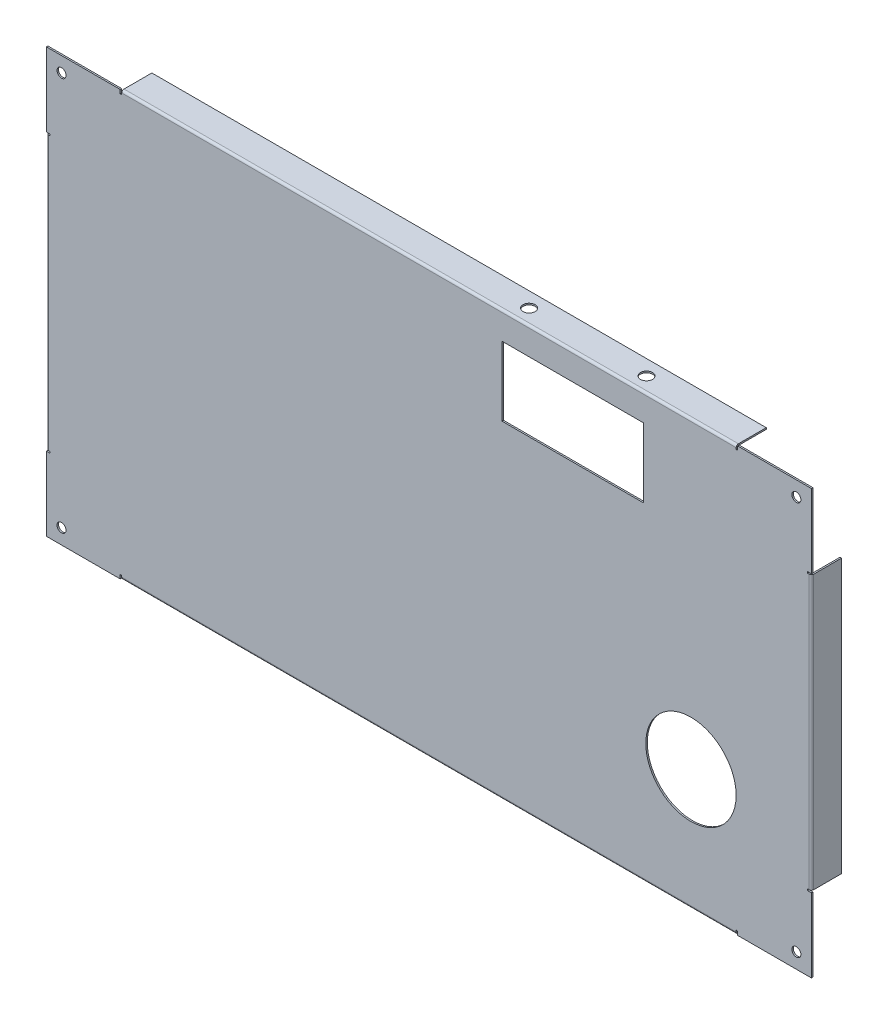
SolidWorks part; units mm, degrees
note: The reader was unsure of these and kept them because the rebuilt part matched: thickness of "基体-法兰1", "边线-法兰1", "边线-法兰2", "边线-法兰3", "边线-法兰4", "钣金1", "钣金6", "钣金7", "钣金8", "钣金9", "钣金10"; flange length of "边线-法兰1", "边线-法兰2", "边线-法兰3", "边线-法兰4".
ref_plane "前视基准面" through (0, 0, 0) normal (0, 0, 1) x (1, 0, 0)
ref_plane "上视基准面" through (0, 0, 0) normal (0, 1, 0) x (1, 0, 0)
ref_plane "右视基准面" through (0, 0, 0) normal (1, 0, 0) x (0, 0, -1)
sketch "草图1" plane through (0, 0, 0) normal (0, 0, 1) x (1, 0, 0)
  line L1 (-254, -140.75) -> (254, -140.75)
  line L2 (-254, -140.75) -> (-254, 140.75)
  line L3 (-254, 140.75) -> (254, 140.75)
  line L4 (254, -140.75) -> (254, 140.75)
  line L5 (-254, -140.75) -> (254, 140.75) construction
  line L6 (-254, 140.75) -> (254, -140.75) construction
  line L7 (48.5, 122.75) -> (142.5, 122.75)
  line L8 (48.5, 122.75) -> (48.5, 76.75)
  line L9 (48.5, 76.75) -> (142.5, 76.75)
  line L10 (142.5, 122.75) -> (142.5, 76.75)
  circle A0 centre (-244, 130.75) radius 3
  circle A1 centre (-244, -130.75) radius 3
  circle A2 centre (244, 130.75) radius 3
  circle A3 centre (244, -130.75) radius 3
  circle A4 centre (174, -60.75) radius 30
  point P0 (0, 0)
  dimension "D11" = 6
  dimension "D14" = 60
  dimension "D1" = 508
  dimension "D2" = 281.5
  dimension "D3" = 10
  dimension "D4" = 10
  dimension "D5" = 10
  dimension "D6" = 10
  dimension "D7" = 10
  dimension "D8" = 10
  dimension "D9" = 10
  dimension "D10" = 10
  dimension "D12" = 80
  dimension "D13" = 80
  dimension "D15" = 46
  dimension "D16" = 94
  dimension "D17" = 64
  dimension "D18" = 111.5
base flange "基体-法兰1" sketch "草图1" thickness 1 reverse thickness direction no parameters "D1"=0.5
edge flange "边线-法兰1" sketch "草图22" flange angle 90 flange length 20 flange position material inside bend radius 0.5 thickness 1 relief rectangular parameters "D6"=10
sketch "草图22" plane through (0, 140.75, -1) normal (0, 1, 0) x (1, 0, 0)
  line L2 (-204, 0) -> (-204, 19)
  line L3 (-204, 19) -> (204, 19)
  line L4 (204, 19) -> (204, 0)
  line L5 (254, 0) -> (-254, 0) construction
  line L6 (204, 0) -> (-204, 0)
  line L7 (-254, 0) -> (-254, -1) construction
  line L8 (254, 0) -> (254, -1) construction
  dimension "D1" = 50
  dimension "D2" = 50
bend "边线折弯1" bend radius 0.5 bend angle 90 parameters "D5"=1
edge flange "边线-法兰2" sketch "草图25" flange angle 90 flange length 20 flange position material inside bend radius 0.5 thickness 1 relief rectangular parameters "D6"=10
sketch "草图25" plane through (-254, 0, -1) normal (-1, 0, 0) x (0, 1, 0)
  line L0 (140.75, 0) -> (-140.75, 0) construction
  line L1 (90.75, 0) -> (-90.75, 0)
  line L2 (-90.75, 0) -> (-90.75, 19)
  line L3 (-90.75, 19) -> (90.75, 19)
  line L4 (90.75, 19) -> (90.75, 0)
  line L5 (140.75, 0) -> (140.75, -1) construction
  line L6 (-140.75, 0) -> (-140.75, -1) construction
  dimension "D1" = 50
  dimension "D2" = 50
bend "边线折弯2" bend radius 0.5 bend angle 90 parameters "D5"=2
edge flange "边线-法兰3" sketch "草图28" flange angle 90 flange length 20 flange position material inside bend radius 0.5 thickness 1 relief rectangular parameters "D6"=10
sketch "草图28" plane through (0, -140.75, -1) normal (0, -1, 0) x (-1, 0, 0)
  line L2 (-204, 0) -> (-204, 19)
  line L3 (-204, 19) -> (204, 19)
  line L4 (204, 19) -> (204, 0)
  line L7 (254, 0) -> (-254, 0) construction
  line L8 (204, 0) -> (-204, 0)
  line L9 (254, 0) -> (254, -1) construction
  line L10 (-254, 0) -> (-254, -1) construction
  dimension "D1" = 50
  dimension "D2" = 50
bend "边线折弯3" bend radius 0.5 bend angle 90 parameters "D5"=3
edge flange "边线-法兰4" sketch "草图31" flange angle 90 flange length 20 flange position material inside bend radius 0.5 thickness 1 relief rectangular parameters "D6"=10
sketch "草图31" plane through (254, 0, -1) normal (1, 0, 0) x (0, -1, 0)
  line L2 (-90.75, 0) -> (-90.75, 19)
  line L3 (-90.75, 19) -> (90.75, 19)
  line L4 (90.75, 19) -> (90.75, 0)
  line L5 (140.75, 0) -> (-140.75, 0) construction
  line L6 (90.75, 0) -> (-90.75, 0)
  line L7 (140.75, 0) -> (140.75, -1) construction
  line L8 (-140.75, 0) -> (-140.75, -1) construction
  dimension "D1" = 50
  dimension "D2" = 50
bend "边线折弯4" bend radius 0.5 bend angle 90 parameters "D5"=4
sketch "草图32" plane through (0, 139.75, 0) normal (0, -1, 0) x (-1, 0, 0)
  circle A0 centre (-134.5, 10) radius 4
  circle A1 centre (-56.5, 10) radius 4
  dimension "D1" = 8
extrude "切除-拉伸1" cut sketch "草图32" against normal through all normal cut yes
sketch "折弯-线1" plane through (0, 0, 0) normal (0, 1, 0) x (1, 0, 0)
sketch "边界框1" plane through (0, 0, 0) normal (0, 1, 0) x (1, 0, 0)
sheet metal parameters "钣金1" thickness 1 parameters "D1"=0.5
flat pattern "平板型式1" [suppressed]
sketch "折弯-线2" plane through (0, 0, 0) normal (0, 1, 0) x (1, 0, 0)
sketch "边界框2" [suppressed] plane through (0, 0, 0) normal (0, 1, 0) x (1, 0, 0)
sheet metal parameters "钣金6" thickness 1 parameters "D1"=0.5, "D7"=0.8
flat pattern "平板型式1" [suppressed]
sketch "折弯-线2" plane through (0, 0, 0) normal (0, 1, 0) x (1, 0, 0)
sketch "边界框2" [suppressed] plane through (0, 0, 0) normal (0, 1, 0) x (1, 0, 0)
bend of the flat pattern "展开-<边线折弯1>1"
sheet metal parameters "钣金7" thickness 1 parameters "D1"=0.5, "D7"=0.8
flat pattern "平板型式1" [suppressed]
sketch "折弯-线2" plane through (0, 0, 0) normal (0, 1, 0) x (1, 0, 0)
sketch "边界框2" [suppressed] plane through (0, 0, 0) normal (0, 1, 0) x (1, 0, 0)
bend of the flat pattern "展开-<边线折弯1>1"
bend of the flat pattern "展开-<边线折弯2>1"
sheet metal parameters "钣金8" thickness 1 parameters "D1"=0.5, "D7"=0.8
flat pattern "平板型式1" [suppressed]
sketch "折弯-线2" plane through (0, 0, 0) normal (0, 1, 0) x (1, 0, 0)
sketch "边界框2" [suppressed] plane through (0, 0, 0) normal (0, 1, 0) x (1, 0, 0)
bend of the flat pattern "展开-<边线折弯1>1"
bend of the flat pattern "展开-<边线折弯2>1"
bend of the flat pattern "展开-<边线折弯3>1"
sheet metal parameters "钣金9" thickness 1 parameters "D1"=0.5, "D7"=0.8
flat pattern "平板型式1" [suppressed]
sketch "折弯-线2" plane through (0, 0, 0) normal (0, 1, 0) x (1, 0, 0)
sketch "边界框2" [suppressed] plane through (0, 0, 0) normal (0, 1, 0) x (1, 0, 0)
bend of the flat pattern "展开-<边线折弯1>1"
bend of the flat pattern "展开-<边线折弯2>1"
bend of the flat pattern "展开-<边线折弯3>1"
bend of the flat pattern "展开-<边线折弯4>1"
sheet metal parameters "钣金10" thickness 1 parameters "D1"=0.5, "D7"=0.8
flat pattern "平板型式1" [suppressed]
sketch "折弯-线2" plane through (0, 0, 0) normal (0, 1, 0) x (1, 0, 0)
sketch "边界框2" [suppressed] plane through (0, 0, 0) normal (0, 1, 0) x (1, 0, 0)
bend of the flat pattern "展开-<边线折弯1>1"
bend of the flat pattern "展开-<边线折弯2>1"
bend of the flat pattern "展开-<边线折弯3>1"
bend of the flat pattern "展开-<边线折弯4>1"
